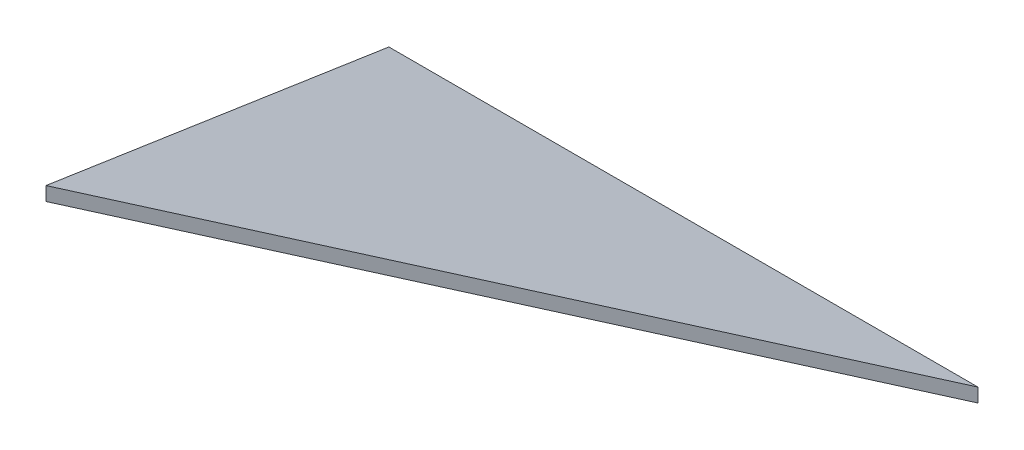
SolidWorks part; units mm, degrees
ref_plane "Front Plane" through (0, 0, 0) normal (0, 0, 1) x (1, 0, 0)
ref_plane "Top Plane" through (0, 0, 0) normal (0, 1, 0) x (1, 0, 0)
ref_plane "Right Plane" through (0, 0, 0) normal (1, 0, 0) x (0, 0, -1)
sketch "Sketch2" plane through (0, 0, 0) normal (0, 1, 0) x (1, 0, 0)
  line L0 (-57.15, 0) -> (224.536, 0)
  line L1 (224.536, 0) -> (-24.3577, -196.7539)
  line L2 (-24.3577, -196.7539) -> (-57.15, 0)
  line L3 (0, 0) -> (0, -152.4) construction
  line L4 (-31.75, -152.4) -> (31.75, -152.4) construction
  point P2 (0, 0)
  dimension "D1" = 281.686
  dimension "D2" = 57.15
  dimension "D3" = 63.5
  dimension "D4" = 152.4
extrude "Boss-Extrude1" add sketch "Sketch2" along normal blind 152.4
ref_plane "Plane1" through (-63.5, 0, 0) normal (1, 0, 0) x (0, 0, -1)
sketch "Sketch3" plane through (-63.5, 0, 0) normal (1, 0, 0) x (0, 0, -1)
  line L0 (0, 76.2) -> (-152.4, 76.2) construction
  line L1 (0, 152.4) -> (0, 0) construction
  line L2 (-152.4, 44.45) -> (-152.4, 107.95) construction
  line L3 (0, 152.4) -> (-152.4, 107.95)
  line L4 (0, 0) -> (-152.4, 44.45)
  line L5 (-152.4, 107.95) -> (-261.2571, 76.2)
  line L6 (-152.4, 44.45) -> (-261.2571, 76.2)
  line L7 (0, 152.4) -> (0, 0)
  point P7 (-152.4, 76.2)
  dimension "D1" = 152.4
  dimension "D2" = 63.5
extrude "Cut-Extrude2" cut sketch "Sketch3" along normal through all flip side to cut
shell "Shell1" thickness 6.35 removed face at (83.693, 76.2, 0)
ref_plane "Plane2" through (0, -12.7, 0) normal (0, 1, 0) x (1, 0, 0)
sketch "Sketch4" plane through (-63.5, 0, 0) normal (1, 0, 0) x (0, 0, -1)
  line L1 (0, 274.6116) -> (-196.7539, 217.2251)
  line L2 (-196.7539, 95.0134) -> (-196.7539, 57.3866) construction
  line L3 (-196.7539, 217.2251) -> (-196.7539, 95.0134) construction
  line L4 (-196.7539, 95.0134) -> (0, 152.4) construction
  line L5 (-196.7539, 57.3866) -> (0, 0) construction
  line L6 (0, 0) -> (0, 6.6146) construction
  line L7 (0, 6.6146) -> (-196.7539, 64.0011)
  line L8 (-196.7539, 64.0011) -> (-196.7539, 57.3866) construction
  line L9 (0, 274.6116) -> (0, 6.6146)
  line L10 (-196.7539, 64.0011) -> (-196.7539, 217.2251)
  dimension "D1" = 6.6146
extrude "Cut-Extrude3" cut sketch "Sketch4" along normal through all
